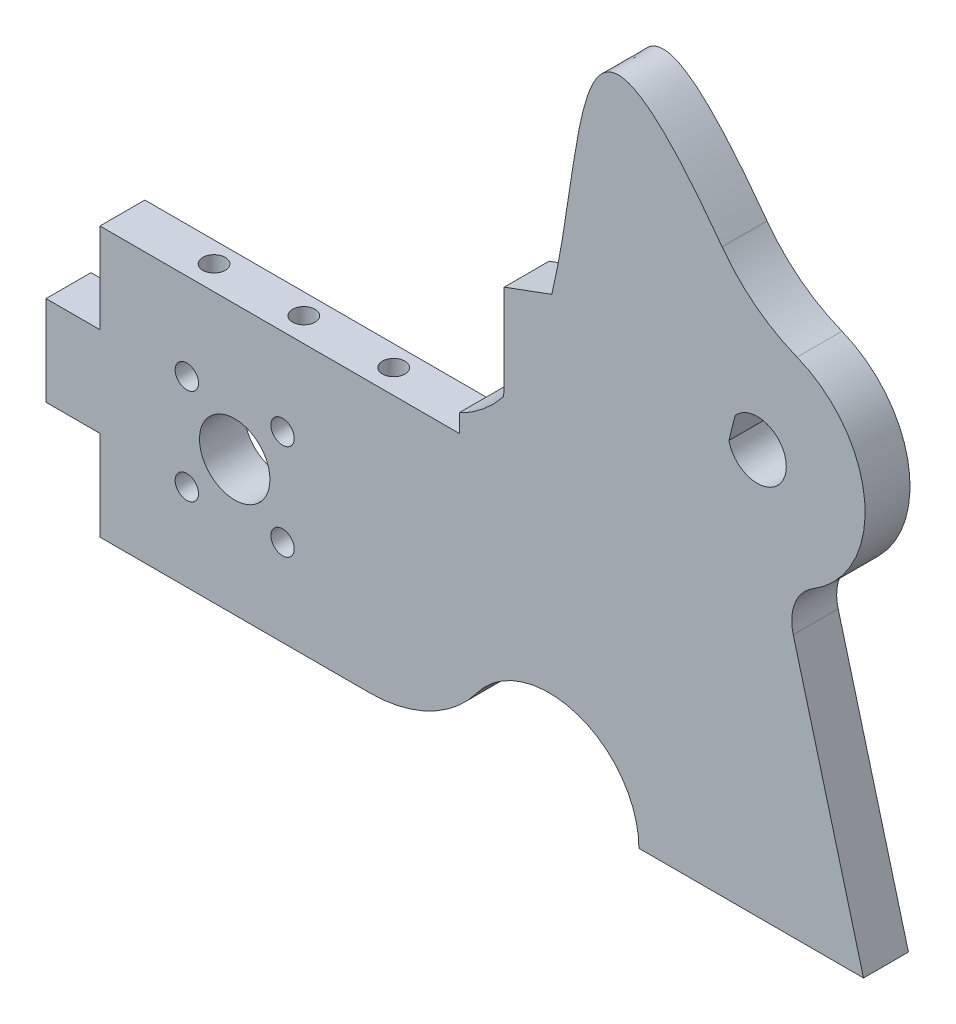
SolidWorks part; units mm, degrees
ref_plane "Front Plane" through (0, 0, 0) normal (0, 0, 1) x (1, 0, 0)
ref_plane "Top Plane" through (0, 0, 0) normal (0, 1, 0) x (1, 0, 0)
ref_plane "Right Plane" through (0, 0, 0) normal (1, 0, 0) x (0, 0, -1)
sketch "Sketch1" plane through (0, 0, 0) normal (0, 0, 1) x (1, 0, 0)
  line L0 (0, 0) -> (107.95, 0)
  line L3 (0, 38.1) -> (0, 25.4)
  line L4 (92.9359, 72.39) -> (0, 38.1)
  line L5 (0, 19.05) -> (100.2273, 19.05) construction
  line L6 (19.05, 19.05) -> (19.05, 28.62) construction
  line L7 (19.05, 19.05) -> (25.817, 25.817) construction
  line L8 (107.95, 0) -> (100.9363, 26.1756)
  line L10 (0, 12.7) -> (0, 0)
  line L11 (0, 25.4) -> (-7.62, 25.4)
  line L13 (0, 12.7) -> (-7.62, 12.7)
  line L14 (-7.62, 25.4) -> (-7.62, 12.7)
  line L15 (100.9363, 26.1756) -> (96.6004, 42.3571)
  arc A0 (96.6004, 42.3571) -> (92.9359, 72.39) centre (92.9359, 57.15) ccw
  circle A1 centre (92.9359, 57.15) radius 4.0957
  circle A2 centre (19.05, 19.05) radius 9.57 construction
  circle A3 centre (25.817, 25.817) radius 1.651
  circle A4 centre (25.817, 12.283) radius 1.651
  circle A5 centre (12.283, 12.283) radius 1.651
  circle A6 centre (12.283, 25.817) radius 1.651
  point P26 (19.05, 19.05)
  dimension "D1" = 8.1915
  dimension "D5" = 15.24
  dimension "D4" = 19.14
  dimension "D7" = 3.302
  dimension "D11" = 99.06
  dimension "D2" = 38.1
  dimension "D3" = 57.15
  dimension "D6" = 107.95
  dimension "D8" = 45
  dimension "D9" = 4
  dimension "D10" = 19.05
  dimension "D12" = 75
  dimension "D14" = 12.7
  dimension "D15" = 12.7
  dimension "D16" = 7.62
extrude "Boss-Extrude1" add sketch "Sketch1" along normal blind 6.35
sketch "Sketch2" plane through (0, 0, 6.35) normal (0, 0, 1) x (1, 0, 0)
  circle A0 centre (92.9359, 57.15) radius 38.1 construction
sketch "Sketch3" plane through (0, 0, 0) normal (-1, 0, 0) x (0, 0, 1)
  line L0 (0, 38.1) -> (6.35, 25.4) construction
  line L1 (6.35, 12.7) -> (0, 0) construction
  circle A0 centre (3.175, 31.75) radius 1.5875
  circle A1 centre (3.175, 6.35) radius 1.5875
  dimension "D1" = 3.175
  dimension "D2" = 3.175
extrude "Cut-Extrude1" cut sketch "Sketch3" against normal blind 6.35
sketch "Sketch6" plane through (0, 0, 6.35) normal (0, 0, 1) x (1, 0, 0)
  line L0 (0, 0) -> (107.95, 0) construction
  line L1 (50.8, 0) -> (76.2, 0)
  arc A0 (76.2, 0) -> (50.8, 0) centre (63.5, 0) ccw
  dimension "D1" = 25.4
  dimension "D2" = 31.75
extrude "Cut-Extrude2" cut sketch "Sketch6" against normal blind 6.35
sketch "Sketch7" plane through (0, 0, 6.35) normal (0, 0, 1) x (1, 0, 0)
  line L0 (12.283, 25.817) -> (25.817, 12.283) construction
  line L1 (12.283, 12.283) -> (25.817, 25.817) construction
  circle A0 centre (19.05, 19.05) radius 4.9784
  dimension "D1" = 9.9568
extrude "Cut-Extrude3" cut sketch "Sketch7" against normal through all
fillet "Fillet1" radius 6.35 1 edges at (96.6004, 42.3571, 3.175)
sketch "Sketch8" plane through (0, 0, 6.35) normal (0, 0, 1) x (1, 0, 0)
  line L1 (0, 38.1) -> (50.8, 38.1)
  line L2 (0, 38.1) -> (0, 76.2)
  line L3 (0, 76.2) -> (50.8, 76.2)
  line L4 (50.8, 38.1) -> (50.8, 76.2)
  dimension "D1" = 50.8
  dimension "D2" = 38.1
extrude "Cut-Extrude4" cut sketch "Sketch8" against normal blind 50.8
sketch "Sketch9" plane through (0, 0, 6.35) normal (0, 0, 1) x (1, 0, 0)
  line L3 (50.8, 40.64) -> (57.15, 40.64)
  line L5 (57.15, 40.64) -> (50.8, 40.64)
  line L6 (57.15, 40.64) -> (57.15, 66.04)
  line L7 (57.15, 66.04) -> (50.8, 66.04)
  line L8 (50.8, 40.64) -> (50.8, 66.04)
  line L9 (0, 38.1) -> (50.8, 38.1) construction
  line M8 (50.8, 56.8434) -> (50.8, 38.1)
  line M21 (92.9359, 72.39) -> (50.8, 56.8434)
  dimension "D1" = 25.4
  dimension "D2" = 2.54
  dimension "D3" = 6.35
extrude "Cut-Extrude5" cut sketch "Sketch9" against normal blind 19.304 contours L3 L6 M21 M8 region at (54.0464, 49.3406, 6.35)
fillet "Fillet6" radius 6.35 1 edges at (57.15, 40.64, 3.175)
fillet "Fillet8" radius 19.05 1 edges at (50.8, 0, 3.175)
sketch "Sketch10" plane through (0, 0, 0) normal (0, -1, 0) x (1, 0, 0)
  line L0 (76.2, 6.35) -> (107.95, 6.35) construction
  line L1 (0, 6.35) -> (0, 0) construction
  line L2 (0, 6.35) -> (38.1, 6.35) construction
  line L3 (107.95, 6.35) -> (107.95, 0) construction
  line L4 (76.2, 0) -> (76.2, 6.35) construction
  circle A0 centre (97.79, 3.175) radius 1.5875
  circle A1 centre (86.36, 3.175) radius 1.5875
  circle A2 centre (31.75, 3.175) radius 1.5875
  circle A3 centre (12.7, 3.175) radius 1.5875
  dimension "D1" = 3.175
  dimension "D2" = 3.175
  dimension "D3" = 3.175
  dimension "D4" = 3.175
  dimension "D5" = 12.7
  dimension "D6" = 19.05
  dimension "D7" = 10.16
  dimension "D8" = 10.16
  dimension "D9" = 11.43
  dimension "D10" = 3.175
  dimension "D11" = 3.175
extrude "Cut-Extrude6" cut sketch "Sketch10" against normal blind 6.35
sketch "Sketch11" plane through (0, 38.1, 0) normal (0, 1, 0) x (1, 0, 0)
  line L0 (0, -6.35) -> (0, 0) construction
  line L1 (50.8, 0) -> (50.8, -6.35) construction
  line L2 (0, -6.35) -> (50.8, -6.35) construction
  circle A0 centre (12.7, -2.9224) radius 1.5875
  circle A1 centre (25.4, -2.9224) radius 1.5875
  circle A2 centre (38.1, -2.9224) radius 1.5875
  dimension "D1" = 3.175
  dimension "D2" = 3.175
  dimension "D3" = 3.175
  dimension "D4" = 12.7
  dimension "D5" = 12.7
  dimension "D6" = 12.7
  dimension "D7" = 12.7
  dimension "D8" = 3.4276
extrude "Cut-Extrude7" cut sketch "Sketch11" against normal blind 6.35
sketch "Sketch12" plane through (0, 0, 6.35) normal (0, 0, 1) x (1, 0, 0)
  line L0 (107.95, 0) -> (146.812, 0) construction
  line L1 (2.0407, 59.7246) -> (71.9905, 88.9761) construction
  line L2 (95.3675, 40.64) -> (71.9905, 88.9761) construction
  line L3 (71.9905, 88.9761) -> (70.6082, 91.8344) construction
  line L4 (50.8, 40.64) -> (85.0271, 40.64)
  line L5 (85.0271, 40.64) -> (92.9359, 72.39)
  arc A0 (61.8128, 49.6242) -> (56.8883, 45.1859) centre (62.9766, 43.3817) ccw construction
  circle A1 centre (19.05, 19.05) radius 44.0879 construction
  circle A2 centre (92.9359, 57.15) radius 38.1 construction
  circle A3 centre (71.9905, 88.9761) radius 3.175 construction
  spline S0 degree 3 poles (50.8, 40.64) (77.2406, 53.2667) (54.8183, 129.1906) (92.9359, 72.39) knots 0 0 0 0 1 1 1 1
  dimension "D2" = 6.35
  dimension "D1" = 38.862
extrude "Boss-Extrude2" add sketch "Sketch12" against normal blind 6.35
fillet "Fillet9" radius 24.13 1 edges at (92.9359, 72.39, 3.175)
